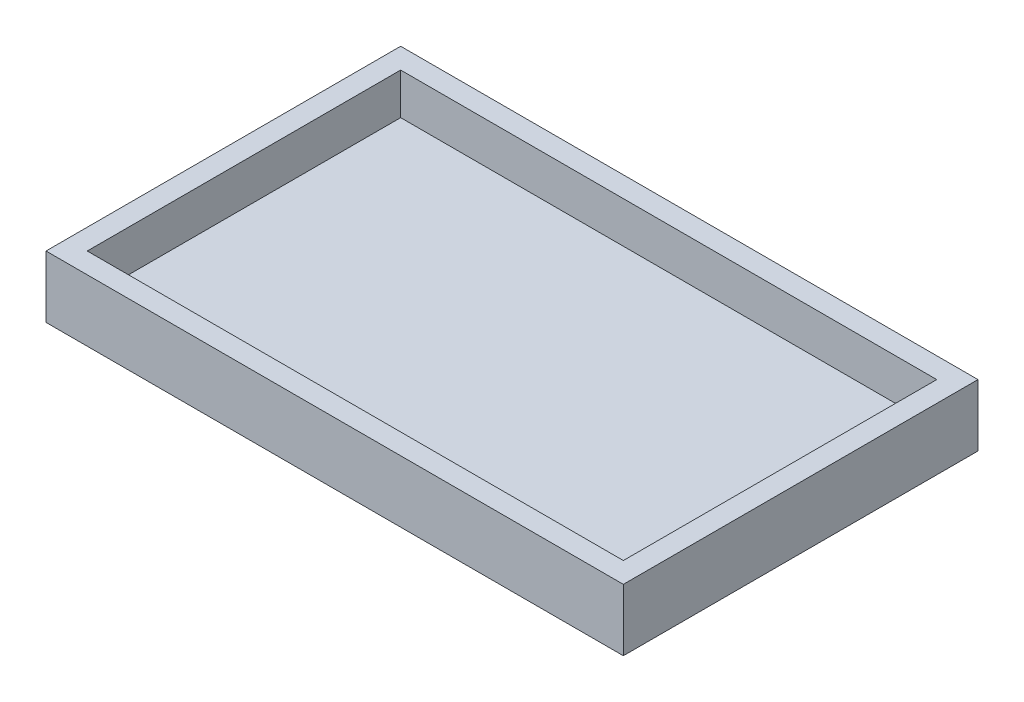
SolidWorks part; units mm, degrees
ref_plane "Front Plane" through (0, 0, 0) normal (0, 0, 1) x (1, 0, 0)
ref_plane "Top Plane" through (0, 0, 0) normal (0, 1, 0) x (1, 0, 0)
ref_plane "Right Plane" through (0, 0, 0) normal (1, 0, 0) x (0, 0, -1)
sketch "Sketch1" plane through (0, 0, 0) normal (0, 1, 0) x (1, 0, 0)
  line L0 (-35.56, -21.844) -> (-35.56, 21.844)
  line L1 (-33.02, -19.304) -> (33.02, -19.304)
  line L2 (-33.02, -19.304) -> (-33.02, 19.304)
  line L3 (-33.02, 19.304) -> (33.02, 19.304)
  line L4 (33.02, -19.304) -> (33.02, 19.304)
  line L5 (-33.02, -19.304) -> (33.02, 19.304) construction
  line L6 (-33.02, 19.304) -> (33.02, -19.304) construction
  line L7 (-35.56, 21.844) -> (35.56, 21.844)
  line L8 (35.56, -21.844) -> (35.56, 21.844)
  line L9 (-35.56, -21.844) -> (35.56, -21.844)
  point P0 (0, 0)
  dimension "D1" = 66.04
  dimension "D2" = 38.608
  dimension "D3" = 2.54
extrude "Boss-Extrude1" add sketch "Sketch1" along normal blind 7.62
extrude "Boss-Extrude2" add sketch "Sketch1<2>" along normal blind 2.54 contours L3 L4 L1 L2
sketch "Sketch1<2>" plane through (0, 0, 0) normal (0, 1, 0) x (1, 0, 0) same geometry as "Sketch1"
